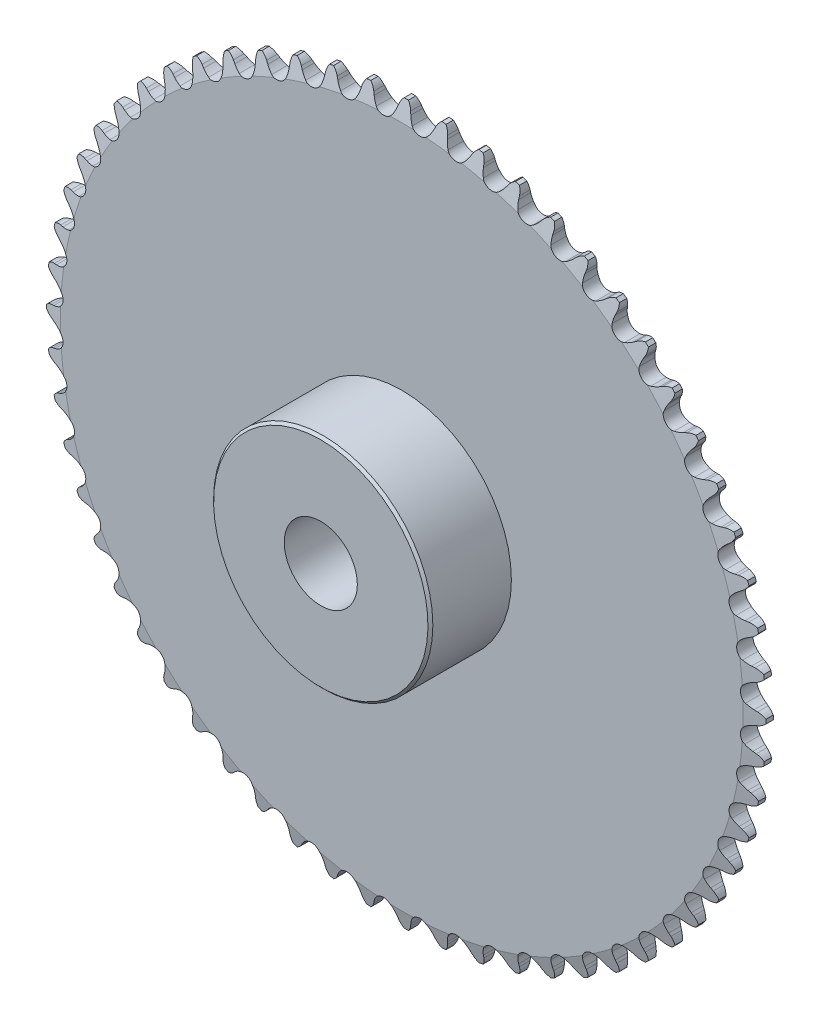
SolidWorks part; units mm, degrees
ref_plane "Front Plane" through (0, 0, 0) normal (0, 0, 1) x (1, 0, 0)
ref_plane "Top Plane" through (0, 0, 0) normal (0, 1, 0) x (1, 0, 0)
ref_plane "Right Plane" through (0, 0, 0) normal (1, 0, 0) x (0, 0, -1)
sketch "Sketch0" plane through (0, 0, 0) normal (0, 0, 1) x (1, 0, 0)
  line L0 (4.7625, -90.8739) -> (0, 0) construction
  line L1 (0, 0) -> (14.2353, -89.8783) construction
  line L2 (0, 0) -> (-4.7625, -90.8739) construction
  line L3 (4.7625, -90.8739) -> (14.2353, -89.8783) construction
  line L4 (4.7625, -90.8739) -> (-4.7625, -90.8739) construction
  line L5 (8.0611, -91.6504) -> (7.7773, -90.9457)
  line L6 (4.7625, -90.8739) -> (0, -91.1235) construction
  line L7 (1.5632, -91.9909) -> (1.7717, -91.2605)
  line L8 (0, -90.8739) -> (0, -93.7314) construction
  line L9 (6.7759, -89.2435) -> (1.6042, -93.4315) construction
  line L10 (0, 0) -> (0, -90.8739) construction
  line L11 (7.7773, -90.9457) -> (1.6042, -93.4315) construction
  line L12 (0, -93.7314) -> (0, -94.1961) construction
  line L13 (11.8355, -90.1305) -> (8.0611, -91.6504) construction
  circle A0 centre (0, 0) radius 93.7314 construction
  circle A1 centre (0, 0) radius 90.9986 construction
  arc A2 (-2.4547, -94.9416) -> (12.3653, -94.1649) centre (0, 0) ccw
  circle A3 centre (0, 0) radius 94.1961 construction
  circle A4 centre (4.7625, -90.8739) radius 2.54 construction
  arc A7 (6.7759, -89.2435) -> (2.5897, -89.4629) centre (4.7625, -90.8739) ccw
  circle A8 centre (4.7625, -90.8739) radius 2.5908 construction
  arc A9 (8.0611, -91.6504) -> (12.3653, -94.1649) centre (11.8355, -90.1305) ccw
  arc A10 (7.7773, -90.9457) -> (6.7759, -89.2435) centre (1.6042, -93.4315) ccw
  arc A11 (1.5632, -91.9909) -> (-2.4547, -94.9416) centre (-2.3495, -90.8739) cw
  arc A12 (1.7717, -91.2605) -> (2.5897, -89.4629) centre (8.1709, -93.0873) cw
  dimension "D1" = 2.5908
  dimension "Dr" = 5.08
  dimension "Ds" = 5.1816
  dimension "R" = 2.5908
  dimension "Pitch" = 9.525
  dimension "A" = 36
  dimension "360/N" = 6
  dimension "B" = 17.067
  dimension "ab" = 7.112
  dimension "J" = 2.8575
  dimension "ac" = 4.064
sketch "Sketch1" plane through (0, 0, 0) normal (1, 0, 0) x (0, 0, -1)
  line L0 (2.1463, 0) -> (-2.1463, 0)
  line L1 (-2.1463, 0) -> (-2.1463, 88.9689)
  line L2 (-2.1463, 88.9689) -> (-0.9557, 93.7314)
  line L3 (-0.9557, 93.7314) -> (0.9557, 93.7314)
  line L4 (0.9557, 93.7314) -> (2.1463, 88.9689)
  line L5 (2.1463, 88.9689) -> (2.1463, 0)
  line L7 (0, 93.7314) -> (0, 0) construction
  line L8 (-2.1463, 88.9689) -> (2.1463, 88.9689) construction
  line L9 (0, 93.7314) -> (0, -93.7314) construction
  line L10 (-2.1463, 88.9689) -> (-2.1463, 93.7314) construction
  line L11 (-2.1463, 93.7314) -> (-0.9557, 93.7314) construction
  line L12 (0.9557, 93.7314) -> (2.1463, 93.7314) construction
  line L13 (2.1463, 93.7314) -> (2.1463, 88.9689) construction
  line L14 (0, 0) -> (-6.4008, 0) construction
  line L22 (2.1463, 0) -> (-23.2537, 0) construction
  line L24 (-2.1463, 0) -> (-2.1463, 85.7304) construction
  dimension "t" = 4.2926
  dimension "g" = 1.1906
  dimension "h" = 4.7625
  dimension "K" = 6.4008
  dimension "MHD" = 171.4608
  dimension "Width" = 25.4
revolve "Revolve1" add sketch "Sketch1" angle 360 mid plane about L0
extrude "Cut-Extrude1" cut sketch "Sketch0" against normal through all and the other way through all
pattern_circular "CirPattern1" count 60 over 360 about axis through (0, 0, -2.1463) along (0, 0, -1) of "Cut-Extrude1"
sketch "Sketch2" plane through (0, 0, 0) normal (0, 0, 1) x (1, 0, 0)
  circle A0 centre (0, 0) radius 9.525 construction
  circle A1 centre (0, 0) radius 28.575
  circle A2 centre (0, 0) radius 93.726 construction
  dimension "Bore" = 19.05
  dimension "Hub Dia." = 57.15
  dimension "OD" = 187.452
extrude "Boss-Extrude1" add sketch "Sketch2" along normal up to vertex (23.2537 mm away) from surface up to point (0, 0, 23.2537) starting at face at (0, 0, 2.1463)
sketch "Sketch3" plane through (0, 0, 0) normal (0, 0, 1) x (1, 0, 0)
  circle A0 centre (0, 0) radius 9.525 construction
  circle A1 centre (0, 0) radius 9.525
extrude "Cut-Extrude2" cut sketch "Sketch3" along normal through all and the other way through all
sketch "Sketch4" plane through (0, 0, 0) normal (1, 0, 0) x (0, 0, -1)
  line L0 (-23.2537, 28.575) -> (-23.2537, 27.94)
  line L1 (-2.1463, 93.7314) -> (-5.3658, 93.7314)
  line L2 (-2.1463, 93.7314) -> (-2.1463, 85.7304)
  line L3 (-2.1463, 85.7304) -> (-5.3658, 85.7304)
  line L4 (-5.3658, 93.7314) -> (-5.3658, 85.7304)
  line L9 (-23.2537, 27.94) -> (-22.6187, 28.575)
  line L10 (-22.6187, 28.575) -> (-23.2537, 28.575)
  dimension "C" = 0.635
  dimension "D3" = 3.2195
revolve "Cut-Revolve1" cut sketch "Sketch4" angle 360 mid plane about L22
sketch "Sketch5" plane through (0, 0, -2.1463) normal (0, 0, -1) x (-1, 0, 0)
  line L0 (0, 88.9689) -> (0, 91.3502) construction
  line L1 (-13.8525, -13.8525) -> (13.8525, -13.8525)
  line L2 (-13.8525, -13.8525) -> (-13.8525, 13.8525)
  line L3 (-13.8525, 13.8525) -> (13.8525, 13.8525)
  line L4 (13.8525, -13.8525) -> (13.8525, 13.8525)
  line L5 (-13.8525, -13.8525) -> (13.8525, 13.8525) construction
  line L6 (-13.8525, 13.8525) -> (13.8525, -13.8525) construction
  line L7 (0, 91.3502) -> (0, 93.7314) construction
  circle A0 centre (0, 0) radius 91.3502
  circle A1 centre (0, 0) radius 88.9689 construction
  circle A2 centre (0, 0) radius 93.7314 construction
  arc A3 (-28.4421, 89.312) -> (-29.4861, 88.9727) centre (0, 0) ccw construction
  arc A4 (-15.488, 87.6104) -> (-21.4854, 86.3357) centre (0, 0) ccw construction
equation "\"360/N@Sketch0\" = 360/\"Teeth@CirPattern1\""
equation "\"Ds@Sketch0\" = 1.005 * \"Dr@Sketch0\" + 0.003"
equation "\"R@Sketch0\" = 1/2 * \"Ds@Sketch0\""
equation "\"A@Sketch0\" = 35 +  ( 60 / \"Teeth@CirPattern1\" ) "
equation "\"B@Sketch0\" = 18 -  ( 56 / \"Teeth@CirPattern1\" )"
equation "\"ac@Sketch0\" = 0.8 * \"Dr@Sketch0\""
equation "\"ab@Sketch0\" = 1.4 * \"Dr@Sketch0\""
equation "\"J@Sketch0\" = 0.3 * \"Pitch@Sketch0\""
equation "\"h@Sketch1\" = \"Pitch@Sketch0\" / 2"
equation "\"g@Sketch1\" = \"h@Sketch1\" / 4"
equation "\"MHD@Sketch1\" = \"Pitch@Sketch0\" * ( cotan ( 180 / \"Teeth@CirPattern1\" ) - 1 ) - 0.030"
equation "\"D3@Sketch4\" = \"t@Sketch1\" * 3 / 4"
